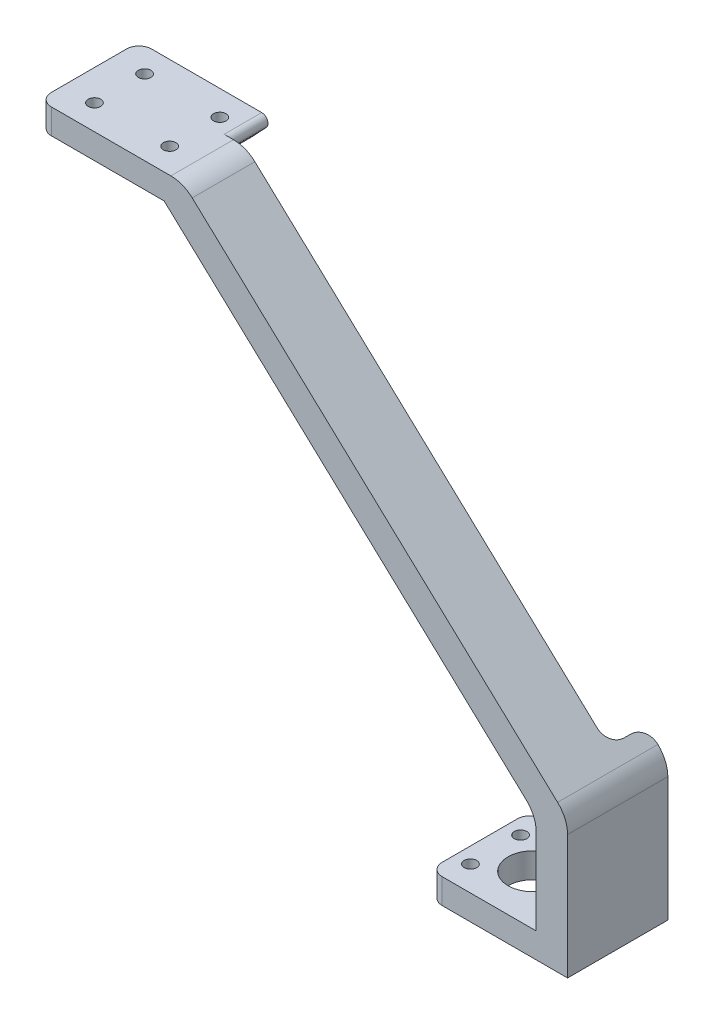
SolidWorks part; units mm, degrees
material "聚脂树脂"
ref_plane "前视基准面" through (0, 0, 0) normal (0, 0, 1) x (1, 0, 0)
ref_plane "上视基准面" through (0, 0, 0) normal (0, 1, 0) x (1, 0, 0)
ref_plane "右视基准面" through (0, 0, 0) normal (1, 0, 0) x (0, 0, -1)
other "Configuration Table"
sketch "草图1" plane through (0, 0, 0) normal (0, 1, 0) x (1, 0, 0)
  line L0 (0, 0) -> (0, 15.4433) construction
  line L1 (-8.5, -8) -> (8.5, -8)
  line L2 (-8.5, -8) -> (-8.5, 8)
  line L3 (-8.5, 8) -> (8.5, 8)
  line L4 (8.5, -8) -> (8.5, 8)
  line L5 (-8.5, -8) -> (8.5, 8) construction
  line L6 (-8.5, 8) -> (8.5, -8) construction
  line L7 (0, 0) -> (21.5354, 0) construction
  circle A0 centre (6, 4) radius 1
  circle A1 centre (-6, 4) radius 1
  circle A2 centre (6, -4) radius 1
  circle A3 centre (-6, -4) radius 1
  circle A4 centre (0, 0) radius 4
  point P0 (0, 0)
  dimension "D3" = 2
  dimension "D4" = 12
  dimension "D5" = 8
  dimension "D6" = 8
  dimension "D1" = 17
  dimension "D2" = 16
extrude "凸台-拉伸1" add sketch "草图1" along normal blind 4
sketch "草图2" plane through (0, 0, 8) normal (0, 0, 1) x (1, 0, 0)
  line L0 (8.5, 4.8259) -> (8.5, 0)
  line L1 (8.5, 4) -> (8.5, 0) construction
  line L2 (-8.5, 0) -> (8.5, 0) construction
  line L3 (8.5, 0) -> (13.5, 0)
  line L4 (13.5, 0) -> (13.5, 22)
  line L6 (-50.6912, 79.2) -> (-70.8814, 79.2)
  line L7 (-70.8814, 79.2) -> (-70.8814, 75.2)
  line L8 (-67, 75.2) -> (-70, 75.2) construction
  line L9 (-70.8814, 75.2) -> (-51, 75.2)
  line L11 (8.5, 19.8259) -> (8.5, 4.8259)
  line L12 (13.5, 22) -> (-47.8395, 79.2)
  line L13 (-47.8395, 79.2) -> (-50.6912, 79.2)
  line L14 (-51, 75.2) -> (-50.8814, 75.2)
  line L15 (-50.8814, 75.2) -> (8.5, 19.8259)
  dimension "D1" = 5
  dimension "D2" = 5
  dimension "D3" = 4
  dimension "D4" = 20
  dimension "D5" = 133
  dimension "D6" = 15
  dimension "D7" = 22
extrude "凸台-拉伸2" add sketch "草图2" against normal blind 16
sketch "草图4" plane through (0, 75.2, 0) normal (0, -1, 0) x (1, 0, 0)
  circle A0 centre (-54, 4) radius 1
  circle A1 centre (-54, -4) radius 1
  circle A2 centre (-66, -4) radius 1
  circle A3 centre (-66, 4) radius 1
  dimension "D1" = 2
  dimension "D2" = 2
  dimension "D3" = 2
  dimension "D4" = 2
extrude "切除-拉伸1" cut sketch "草图4" against normal blind 16
fillet "圆角1" radius 2 4 edges at (-8.5, 2, -8) (-8.5, 2, 8) (-70.8814, 77.2, -8) (-70.8814, 77.2, 8)
fillet "圆角2" radius 5 3 edges at (-47.8395, 79.2, 0) (13.5, 22, 0) (8.5, 19.8259, 0)
sketch "草图7" plane through (17.2523, 18.5009, 0) normal (0.682, 0.7314, 0) x (0, 0, -1)
  line L0 (2, 89.8537) -> (8, 89.8537)
  line L2 (8, 89.8537) -> (8, 9.8537)
  line L3 (8, 9.8537) -> (2, 9.8537)
  line L4 (2, 9.8537) -> (2, 89.8537)
  line L5 (6, 105.8537) -> (-6, 105.8537) construction
  line L6 (8, 7.3048) -> (8, 87.0323) construction
  dimension "D1" = 6
  dimension "D2" = 16
  dimension "D3" = 80
extrude "切除-拉伸2" cut sketch "草图7" against normal blind 10
fillet "圆角3" radius 1 1 edges at (-49.0572, 79.1431, -5)
fillet "圆角4" radius 2.5 2 edges at (8.3408, 23.3927, -8) (8.3408, 23.3927, -2)
